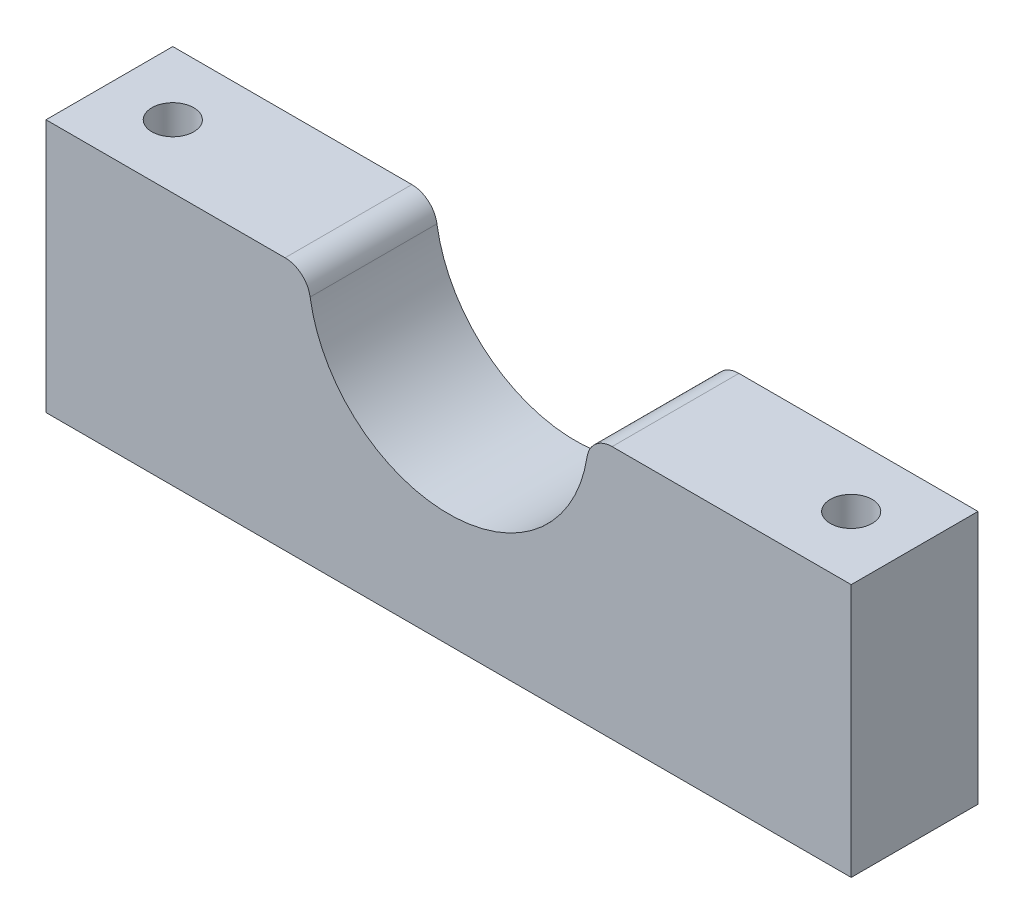
SolidWorks part; units mm, degrees
ref_plane "Спереди" through (0, 0, 0) normal (0, 0, 1) x (1, 0, 0)
ref_plane "Сверху" through (0, 0, 0) normal (0, 1, 0) x (1, 0, 0)
ref_plane "Справа" through (0, 0, 0) normal (1, 0, 0) x (0, 0, -1)
sketch "Эскиз1" plane through (0, 0, 0) normal (0, 0, 1) x (1, 0, 0)
  line L0 (0, 24.9844) -> (0, -42.4233) construction
  line L1 (11.05, 0) -> (31.75, 0)
  line L2 (-31.75, 0) -> (-11.05, 0)
  line L3 (-31.75, 0) -> (-31.75, -20)
  line L4 (-31.75, -20) -> (31.75, -20)
  line L5 (31.75, 0) -> (31.75, -20)
  line L6 (-31.75, 0) -> (31.75, -20) construction
  line L7 (-31.75, -20) -> (31.75, 0) construction
  arc A0 (-11.05, 0) -> (11.05, 0) centre (0, 0) ccw
  point P5 (0, -10)
  dimension "D1" = 22.1
  dimension "D2" = 63.5
  dimension "D3" = 20
extrude "Бобышка-Вытянуть1" add sketch "Эскиз1" along normal blind 10
sketch "Эскиз2" plane through (0, -20, 0) normal (0, -1, 0) x (1, 0, 0)
  line L0 (-31.75, 5) -> (31.75, 5) construction
  line L1 (-31.75, 10) -> (-31.75, 0) construction
  line L2 (31.75, 10) -> (31.75, 0) construction
  line L3 (-26.75, 10) -> (-26.75, 0) construction
  line L4 (-31.75, 10) -> (31.75, 10) construction
  line L5 (-31.75, 0) -> (31.75, 0) construction
  line L6 (26.75, 10) -> (26.75, 0) construction
  dimension "D1" = 5
  dimension "D2" = 5
hole_wizard "Отверстие обработанное метчиком M4x0.71" positions "Эскиз4" profile "Эскиз3" tap size "M4x0.7" standard "Ansi Metric" end condition through all
sketch "Эскиз4" plane through (0, -20, 0) normal (0, -1, 0) x (-1, 0, 0)
  line L0 (26.75, -10) -> (26.75, 0) construction
  line L1 (-26.75, -10) -> (-26.75, 0) construction
  point P0 (26.75, -5)
  point P4 (-26.75, -5)
sketch "Эскиз3" plane through (-26.75, -20, 5) normal (1, 0, 0) x (0, 0, -1)
  line L0 (0, 0) -> (0, 20)
  line L1 (0, 20) -> (1.65, 20)
  line L2 (1.65, 20) -> (1.65, 0)
  line L5 (1.65, 0) -> (0, 0)
  line L11 (0, -6.35) -> (0, 107.95) construction
  dimension "Диаметр проходного сверла" = 3.3
  dimension "Глубина проходного сверла" = 20
cosmetic thread "Отверстие резьбы1" parameters "D2"=4
cosmetic thread "Отверстие резьбы2" parameters "D2"=4
fillet "Скругление2" radius 2 2 edges at (11.05, 0, 5) (-11.05, 0, 5)
fillet "Скругление1" [suppressed] radius 0.5
